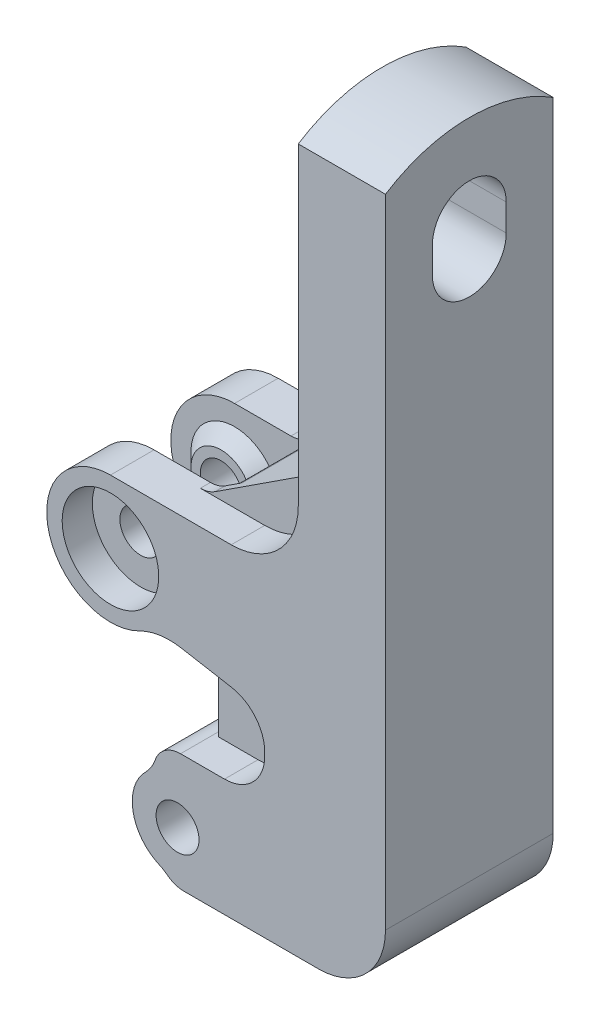
SolidWorks part; units mm, degrees
ref_plane "Płaszczyzna przednia" through (0, 0, 0) normal (0, 0, 1) x (1, 0, 0)
ref_plane "Płaszczyzna górna" through (0, 0, 0) normal (0, 1, 0) x (1, 0, 0)
ref_plane "Płaszczyzna prawa" through (0, 0, 0) normal (1, 0, 0) x (0, 0, -1)
sketch "Szkic1" plane through (0, 0, 0) normal (0, 0, 1) x (1, 0, 0)
  circle A0 centre (0, 0) radius 3.875
  circle A1 centre (0, 0) radius 1.6
  dimension "D1" = 7.75
  dimension "D2" = 3.2
extrude "Dodanie-wyciągnięcie1" add sketch "Szkic1" along normal mid plane 12.5
sketch "Szkic2" plane through (0, 0, 0) normal (0, 0, 1) x (1, 0, 0)
  line L0 (0, -3.875) -> (15.5, -3.875)
  line L1 (-2, 3.319) -> (-2, 4.875)
  line L2 (15.5, -3.875) -> (15.5, 48.625)
  line L3 (15.5, 48.625) -> (6.5, 48.625)
  line L4 (6.5, 48.625) -> (6.5, 20.25)
  line L5 (-5, 15.5) -> (0, 0) construction
  line L6 (-2, 4.875) -> (6.5, 4.875)
  line L7 (6.5, 4.875) -> (6.5, 10.625)
  line L8 (6.5, 10.625) -> (-1.7111, 12.0728)
  line L10 (6.5, 20.25) -> (-5, 20.25)
  circle A1 centre (0, 0) radius 3.875 construction
  arc A2 (-2, 3.319) -> (0, -3.875) centre (0, 0) ccw
  arc A3 (-5, 20.25) -> (-1.7111, 12.0728) centre (-5, 15.5) ccw
  circle A4 centre (-5, 15.5) radius 1.55
  circle A6 centre (0, 0) radius 1.6 construction
  circle A7 centre (0, 0) radius 1.6
  dimension "D1" = 2
  dimension "D2" = 9.5
  dimension "D3" = 3.1
  dimension "D4" = 8.75
  dimension "D5" = 8.5
  dimension "D6" = 9
  dimension "D7" = 100
  dimension "D8" = 5.75
  dimension "D9" = 52.5
extrude "Dodanie-wyciągnięcie3" add sketch "Szkic2" along normal mid plane 12.5
sketch "Szkic3" plane through (0, 0, 0) normal (0, 0, 1) x (1, 0, 0)
  line L0 (-2, 4.875) -> (-2, 3.319) construction
  line L1 (-2, 4.875) -> (-2, 3.319)
  line L2 (-1.5, 4.875) -> (-1.5, 3.0233)
  line L3 (-2, 4.875) -> (-1.5, 4.875)
  line L4 (0, -3.875) -> (0, -3.375)
  circle A0 centre (0, 0) radius 3.875 construction
  arc A1 (-2, 3.319) -> (0, -3.875) centre (0, 0) ccw
  arc A2 (-1.5, 3.0233) -> (0, -3.375) centre (0, 0) ccw
  dimension "D1" = 0.5
extrude "Wytnij-wyciągnięcie1" cut sketch "Szkic3" against normal through all both and the other way through all
sketch "Szkic4" plane through (0, 0, 0) normal (0, 0, 1) x (1, 0, 0)
  circle A0 centre (-5, 15.5) radius 6.75
  dimension "D1" = 13.5
extrude "Wytnij-wyciągnięcie2" cut sketch "Szkic4" against normal mid plane 6
sketch "Szkic5" plane through (0, 0, 6.25) normal (0, 0, 1) x (1, 0, 0)
  line L1 (-3.2679, 18.5) -> (-6.7321, 18.5)
  line L2 (-6.7321, 18.5) -> (-8.4641, 15.5)
  line L3 (-8.4641, 15.5) -> (-6.7321, 12.5)
  line L4 (-6.7321, 12.5) -> (-3.2679, 12.5)
  line L5 (-3.2679, 12.5) -> (-1.5359, 15.5)
  line L6 (-1.5359, 15.5) -> (-3.2679, 18.5)
  circle A0 centre (-5, 15.5) radius 3 construction
  dimension "D1" = 6
extrude "Wytnij-wyciągnięcie3" cut sketch "Szkic5" against normal blind 2
sketch "Szkic6" plane through (0, 0, -6.25) normal (0, 0, -1) x (-1, 0, 0)
  circle A0 centre (5, 15.5) radius 3.6
  dimension "D1" = 7.2
extrude "Wytnij-wyciągnięcie4" cut sketch "Szkic6" against normal blind 2.25
sketch "Szkic7" plane through (0, 0, 3) normal (0, 0, -1) x (-1, 0, 0)
  circle A0 centre (5, 15.5) radius 1.55 construction
  circle A1 centre (5, 15.5) radius 1.55
  circle A2 centre (5, 15.5) radius 2.25
  dimension "D1" = 4.5
extrude "Dodanie-wyciągnięcie4" add sketch "Szkic7" along normal blind 1
mirror "Lustro1" about plane through (0, 0, 0) normal (0, 0, 1) of "Dodanie-wyciągnięcie4"
chamfer "Sfazowanie2" distance 1 angle 45 2 edges at (-2.75, 15.5, 3) (-2.75, 15.5, -3)
chamfer "Sfazowanie1" distance 1 angle 45 1 edges at (0, -3.375, 0)
fillet "Zaokrąglenie2" radius 3 2 edges at (-1.5, 3.0233, 0) (-0.7714, -3.2857, 0)
fillet "Zaokrąglenie3" radius 2 1 edges at (-0.3044, -3.875, 0)
fillet "Zaokrąglenie4" radius 2 1 edges at (-1.5, 4.875, 0)
fillet "Zaokrąglenie6" radius 5 1 edges at (15.5, -3.875, 0)
sketch "Szkic8" plane through (0, 0, 0) normal (0, 0, 1) x (1, 0, 0)
  line L0 (6.5, 4.875) -> (6.5, 10.625)
  line L1 (6.5, 10.625) -> (0.5599, 11.6724)
  line L2 (-1.7111, 12.0728) -> (6.5, 10.625) construction
  line L3 (0.5599, 11.6724) -> (0.5599, 4.875)
  line L4 (6.5, 4.875) -> (0.2232, 4.875) construction
  line L5 (0.5599, 4.875) -> (6.5, 4.875)
  arc A0 (0.5599, 11.6724) -> (-0.2042, 20.25) centre (-5, 15.5) ccw construction
extrude "Dodanie-wyciągnięcie5" add sketch "Szkic8" along normal mid plane 7.5
sketch "Szkic10" plane through (15.5, 0, 0) normal (1, 0, 0) x (0, 0, -1)
  line L0 (0, 43.625) -> (0, 41.625) construction
  line L1 (2.75, 43.625) -> (2.75, 41.625)
  line L2 (-2.75, 43.625) -> (-2.75, 41.625)
  line L3 (0, 46.375) -> (0, 48.625) construction
  line L4 (-6.25, 48.625) -> (6.25, 48.625) construction
  arc A0 (2.75, 43.625) -> (-2.75, 43.625) centre (0, 43.625) ccw
  arc A1 (-2.75, 41.625) -> (2.75, 41.625) centre (0, 41.625) ccw
  point P3 (0, 42.625)
  dimension "D1" = 2.75
  dimension "D2" = 2.25
  dimension "D3" = 2
extrude "Wytnij-wyciągnięcie5" cut sketch "Szkic10" against normal up to next
sketch "Szkic11" plane through (15.5, 0, 0) normal (1, 0, 0) x (0, 0, -1)
  line L0 (-6.25, 48.625) -> (6.25, 48.625)
  arc A0 (-6.25, 48.625) -> (6.25, 48.625) centre (0, 38.875) cw
  arc A1 (-2.75, 41.625) -> (2.75, 41.625) centre (0, 41.625) ccw construction
extrude "Dodanie-wyciągnięcie7" add sketch "Szkic11" against normal up to surface (9 mm away) up to face at (6.5, 42.625, 0)
sketch "Szkic12" plane through (0, 0, 6.25) normal (0, 0, 1) x (1, 0, 0)
  line L0 (15.5, 50.4562) -> (6.5, 50.4562) construction
  line L1 (9, 50.4562) -> (6.5, 50.4562)
  line L2 (9, 50.4562) -> (9, 20.25)
  line L3 (9, 20.25) -> (6.5, 20.25)
  line L4 (6.5, 50.4562) -> (6.5, 20.25)
  line L5 (6.5, 48.625) -> (6.5, 20.25) construction
  dimension "D1" = 2.5
extrude "Wytnij-wyciągnięcie6" cut sketch "Szkic12" against normal up to next
sketch "Szkic9" plane through (0, 0, 0) normal (0, 0, 1) x (1, 0, 0)
  line L0 (9, 26.25) -> (-0.2042, 20.25)
  line L2 (9, 20.25) -> (-5, 20.25) construction
  line L3 (-0.2042, 20.25) -> (9, 20.25)
  line L4 (9, 20.25) -> (9, 26.25)
  line L5 (9, 20.25) -> (9, 48.625) construction
  arc A0 (0.5599, 11.6724) -> (-0.2042, 20.25) centre (-5, 15.5) ccw construction
  dimension "D1" = 6
extrude "Dodanie-wyciągnięcie6" add sketch "Szkic9" along normal mid plane 7.5
fillet "Zaokrąglenie11" radius 5 2 edges at (9, 20.25, 5) (9, 20.25, -5)
fillet "Zaokrąglenie8" radius 2 2 edges at (0.5599, 11.6724, 0) (-0.2042, 20.25, 0)
fillet "Zaokrąglenie9" radius 2 2 edges at (-0.2042, 20.25, 3.375) (-0.2042, 20.25, -3.375)
fillet "Zaokrąglenie10" radius 5 2 edges at (-1.7111, 12.0728, -4.625) (-1.7111, 12.0728, 4.625)
fillet "Zaokrąglenie7" radius 3 4 edges at (6.5, 10.625, 5) (6.5, 10.625, -5) (6.5, 4.875, -5) (6.5, 4.875, 5)
fillet "Zaokrąglenie12" radius 5 1 edges at (9, 26.25, 0)
mirror "Lustro2" about plane through (0, 0, 0) normal (0, 0, 1) of bodies 111 114
delete or keep bodies "Obiekt-Usuń/zachowaj 1" type keep bodies bodies 115
